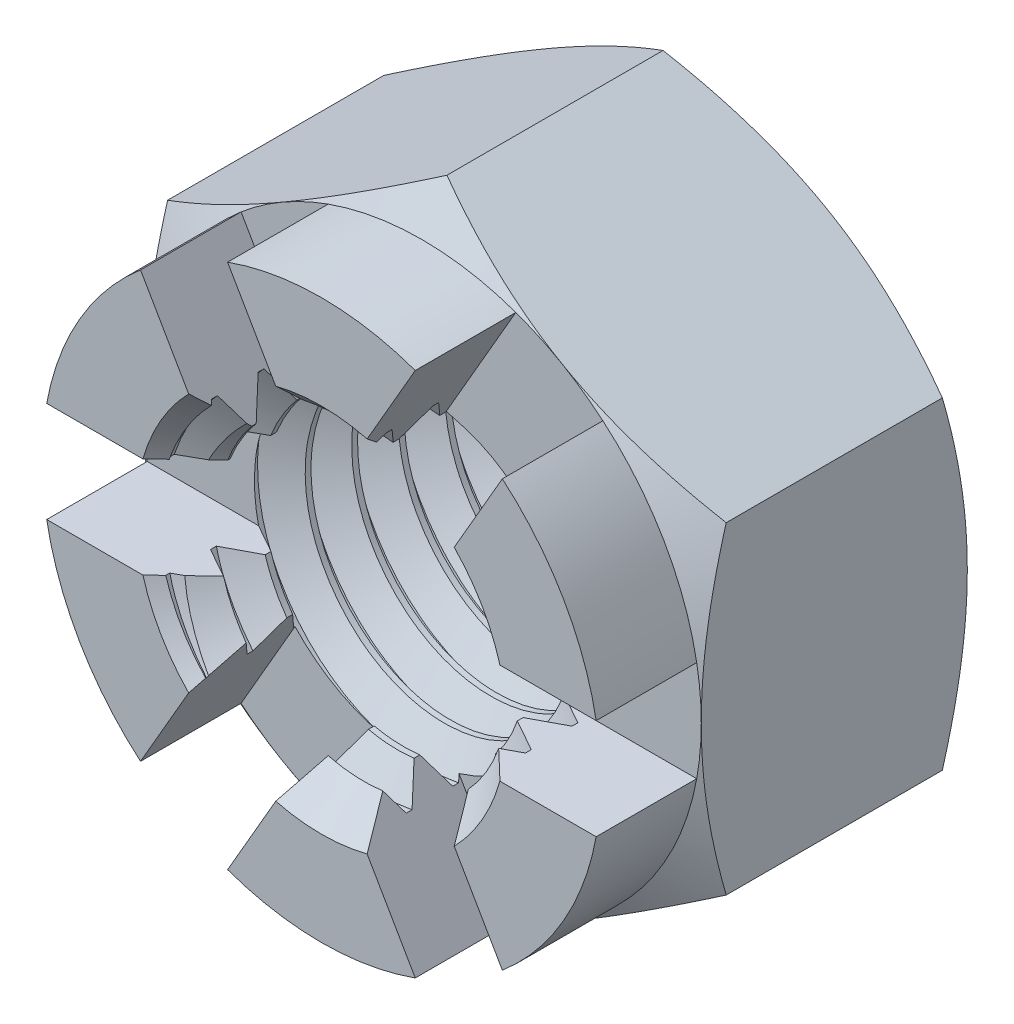
SolidWorks part; units mm, degrees
ref_plane "Front Plane" through (0, 0, 0) normal (0, 0, 1) x (1, 0, 0)
ref_plane "Top Plane" through (0, 0, 0) normal (0, 1, 0) x (1, 0, 0)
ref_plane "Right Plane" through (0, 0, 0) normal (1, 0, 0) x (0, 0, -1)
sketch "Sketch1" plane through (0, 0, 0) normal (0, 0, 1) x (1, 0, 0)
  line L1 (0, 7.3323) -> (-6.35, 3.6662)
  line L2 (-6.35, 3.6662) -> (-6.35, -3.6662)
  line L3 (-6.35, -3.6662) -> (0, -7.3323)
  line L4 (0, -7.3323) -> (6.35, -3.6662)
  line L5 (6.35, -3.6662) -> (6.35, 3.6662)
  line L6 (6.35, 3.6662) -> (0, 7.3323)
  circle A0 centre (0, 0) radius 6.35 construction
  dimension "Hex" = 12.7
extrude "Extrude1" add sketch "Sketch1" against normal blind 8.3344
sketch "Sketch2" plane through (0, 0, 0) normal (0, 0, 1) x (1, 0, 0)
  circle A0 centre (0, 0) radius 6.35 construction
  circle A1 centre (0, 0) radius 6.35
sketch "Sketch3" plane through (0, 0, -8.3344) normal (0, 0, -1) x (-1, 0, 0)
  circle A1 centre (0, 0) radius 6.35
  circle A2 centre (0, 0) radius 6.35
  dimension "D1" = 0
extrude "Cut-Extrude2" cut sketch "Sketch3" against normal through all draft 60 flip side to cut
sketch "Sketch4" plane through (0, 0, 0) normal (0, 0, 1) x (1, 0, 0)
  circle A0 centre (0, 0) radius 3.9624
  dimension "Thread Dia" = 7.9248
extrude "Cut-Extrude3" cut sketch "Sketch4" against normal through all
sketch "Sketch7" plane through (0, 0, 0) normal (0, 0, 1) x (1, 0, 0)
  circle A4 centre (0, 0) radius 4.2164
  circle A5 centre (0, 0) radius 4.2164
  dimension "D1" = 0.254
sketch "Sketch8" plane through (0, 0, -8.3344) normal (0, 0, -1) x (-1, 0, 0)
  circle A1 centre (0, 0) radius 4.2164
  circle A2 centre (0, 0) radius 4.2164 construction
sketch "Sketch5" plane through (0, 0, 0) normal (0, 0, 1) x (1, 0, 0)
  circle A0 centre (0, 0) radius 3.9624 construction
  circle A1 centre (0, 0) radius 3.9624
curve "Helix/Spiral1" pitch 1.0583 height 9.3927 turns 8.875 parameters "pitch"=1.0583
sketch "Sketch9" plane through (0, 0, 0) normal (1, 0, 0) x (0, 0, -1)
  line L0 (-0.5292, 3.9624) -> (-0.3969, 3.9624)
  line L1 (-0.3969, 3.9624) -> (0, 3.275)
  line L2 (-0.5292, 3.9624) -> (-0.926, 3.275)
  line L3 (-0.926, 3.275) -> (0, 3.275)
  line L4 (-0.463, 3.9624) -> (-0.463, 3.275) construction
  line L5 (-0.7276, 3.6187) -> (-0.1984, 3.6187) construction
  line L7 (0, 3.275) -> (0, 3.9624) construction
  line L8 (0, 3.9624) -> (0, -3.9624) construction
  dimension "D1" = 0.1323
  dimension "D2" = 0.5292
  dimension "D3" = 60
sketch "Sketch12" plane through (0, 0, 0) normal (0, 0, 1) x (1, 0, 0)
  circle A0 centre (0, 0) radius 3.275
  circle A1 centre (0, 0) radius 3.9624 construction
  circle A2 centre (0, 0) radius 3.9624
extrude "Extrude2" add sketch "Sketch12" against normal up to surface (8.3344 mm away) up to face at (3.9624, 0, -8.3344)
sweep "Cut-Sweep1" cut profiles "Sketch9" path "Helix/Spiral1"
extrude "Cut-Extrude6" cut sketch "Sketch7" against normal through all draft 45
extrude "Cut-Extrude7" cut sketch "Sketch8" against normal through all draft 45
sketch "Sketch13" plane through (0, 0, 0) normal (0, 0, 1) x (1, 0, 0)
  line L0 (-0.9899, 0.5715) -> (0.9899, -0.5715)
  line L1 (-0.9899, 0.5715) -> (2.1851, 6.0708)
  line L2 (0.9899, -0.5715) -> (4.1649, 4.9278)
  line L3 (2.1851, 6.0708) -> (4.1649, 4.9278)
  line L5 (6.35, 3.6662) -> (0, 7.3323) construction
  dimension "slot width" = 2.286
extrude "Cut-Extrude8" cut sketch "Sketch13" against normal blind 2.286
sketch "Sketch14" plane through (0, 0, -2.286) normal (0, 0, 1) x (1, 0, 0)
  circle A0 centre (0, 0) radius 6.35 construction
  circle A1 centre (0, 0) radius 6.35
extrude "Cut-Extrude9" cut sketch "Sketch14" against normal through all draft 60 flip side to cut
sketch "Sketch15" plane through (0, 0, 0) normal (0, 0, 1) x (1, 0, 0)
  circle A0 centre (0, 0) radius 6.35 construction
  circle A1 centre (0, 0) radius 6.35
extrude "Cut-Extrude10" cut sketch "Sketch15" against normal up to surface (2.286 mm away) flip side to cut up to face at (2.2427, 4.167, -2.286)
pattern_circular "CirPattern1" count 6 over 360 about axis through (0, 0, 0) along (0, 0, 1) of "Cut-Extrude8"
equation "\"D2@Sketch9\" = \"pitch@Helix/Spiral1\"*.5"
equation "\"D3@Helix/Spiral1\" = \"pitch@Helix/Spiral1\"+\"Height@Extrude1\""
equation "\"D1@Sketch9\" = \"pitch@Helix/Spiral1\"*.125"
